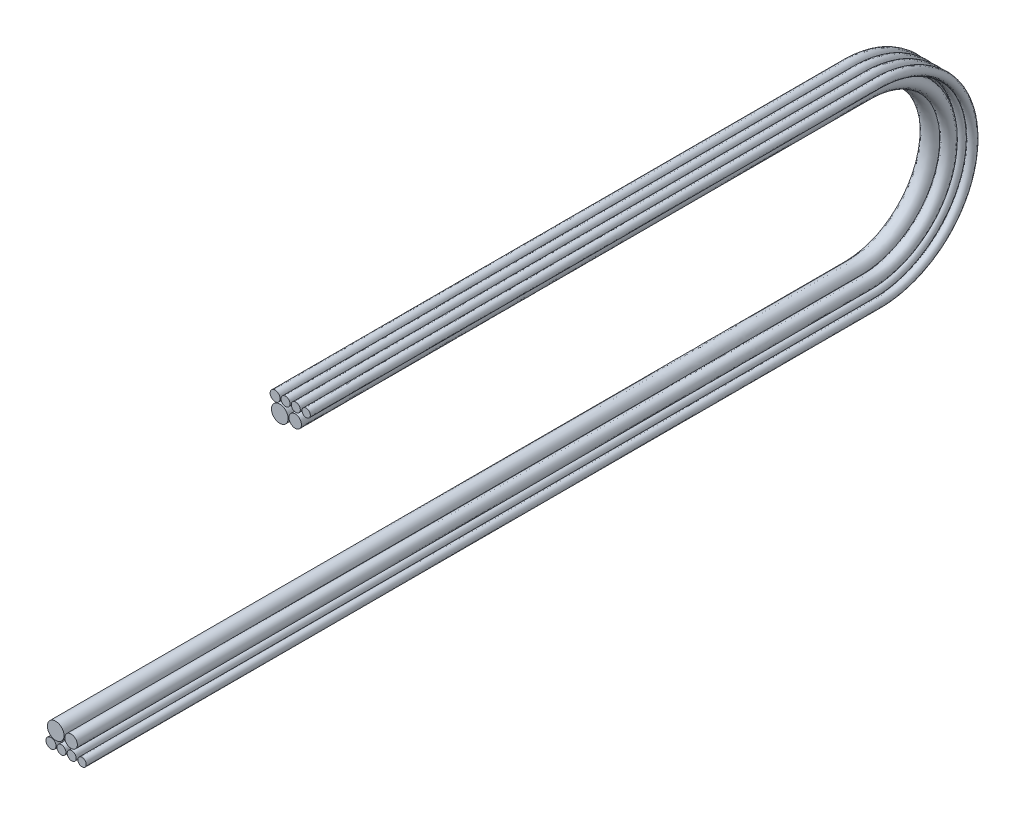
SolidWorks part; units mm, degrees
ref_plane "Front Plane" through (0, 0, 0) normal (0, 0, 1) x (1, 0, 0)
ref_plane "Top Plane" through (0, 0, 0) normal (0, 1, 0) x (1, 0, 0)
ref_plane "Right Plane" through (0, 0, 0) normal (1, 0, 0) x (0, 0, -1)
sketch "Sketch1" plane through (0, 0, 0) normal (0, 0, 1) x (1, 0, 0)
  line L1 (18.5, 18) -> (-18.5, 18) construction
  line L2 (18.5, 18) -> (18.5, 0) construction
  line L3 (18.5, 0) -> (-18.5, 0) construction
  line L4 (-18.5, 18) -> (-18.5, 0) construction
  circle A0 centre (-16.1, 2.4) radius 2.4
  circle A2 centre (-11.0983, 2.15) radius 2.15
  circle A5 centre (-6.1615, 2.15) radius 2.15
  circle A6 centre (-1.1864, 2) radius 2
  circle A7 centre (-13.8535, 8.6823) radius 4
  circle A8 centre (-6.4473, 8.0498) radius 3
  dimension "D3" = 4.8
  dimension "D4" = 4.3
  dimension "D6" = 4
  dimension "D7" = 8
  dimension "D8" = 6
  dimension "D1" = 37
  dimension "D2" = 18
sketch "Sketch2" plane through (0, 0, 0) normal (1, 0, 0) x (0, 0, -1)
  spline S1 degree 3 poles (-999.9965, 9.7) (-539.4622, 9.7) (-78.8558, 9.7) (381.8225, 9.7) (382.0385, 9.7023) (382.1825, 9.7043) (382.2545, 9.7055) (455.7269, 10.9584) (455.7269, 84.4416) (382.2545, 85.6945) (382.1825, 85.6957) (382.0385, 85.6977) (381.8225, 85.7) (-42.9905, 85.7) (-467.7316, 85.7) (-892.4006, 85.7) knots -1.36443 -1.36443 -1.36443 -1.36443 0.520677 0.520972 0.521267 0.521561 0.521561 0.521561 0.625243 0.625243 0.625243 0.625538 0.625833 0.626127 2.364427 2.364427 2.364427 2.364427 weights 1 1 1 1 1 1 1 0.3447 0.3447 1 1 1 1 1 1 1 only from (0, 9.7) to (107.5936, 85.7) construction
  spline S2 degree 3 poles (0, 9.7) (127.2022, 9.7) (254.4764, 9.7) (381.8225, 9.7) (382.0385, 9.7023) (382.1825, 9.7043) (382.2545, 9.7055) (455.7269, 10.9584) (455.7269, 84.4416) (382.2545, 85.6945) (382.1825, 85.6957) (382.0385, 85.6977) (381.8225, 85.7) (290.3409, 85.7) (198.9313, 85.7) (107.5936, 85.7) knots 0 0 0 0 0.520677 0.520972 0.521267 0.521561 0.521561 0.521561 0.625243 0.625243 0.625243 0.625538 0.625833 0.626127 1 1 1 1 weights 1 1 1 1 1 1 1 0.3447 0.3447 1 1 1 1 1 1 1
sweep "Sweep1" add profiles "Sketch1" path "Sketch2"
